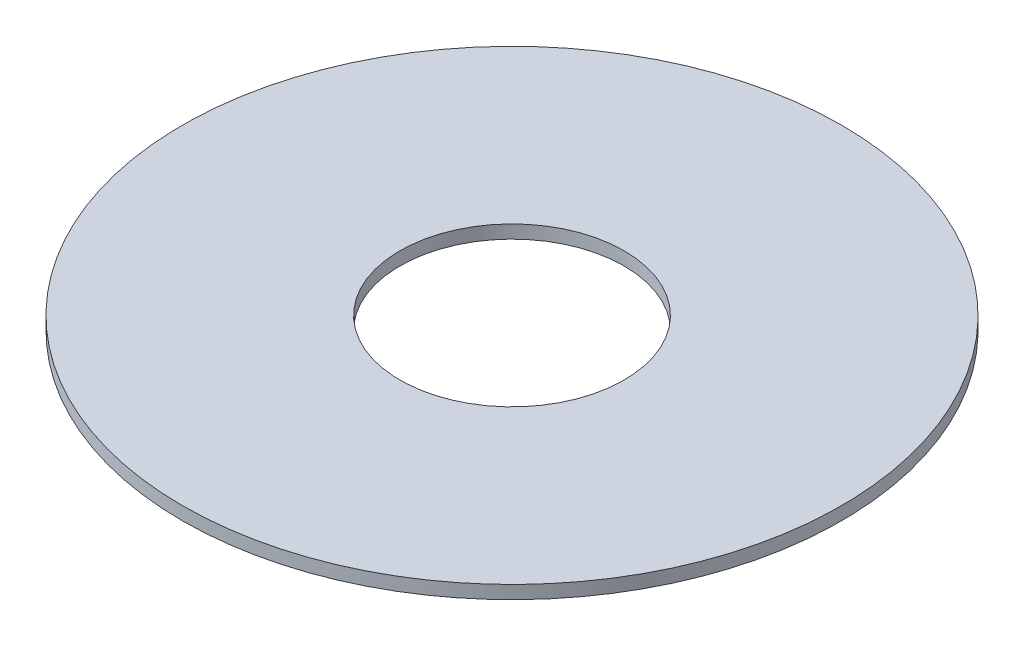
SolidWorks part; units mm, degrees
material "AISI 304"
ref_plane "Front Plane" through (0, 0, 0) normal (0, 0, 1) x (1, 0, 0)
ref_plane "Top Plane" through (0, 0, 0) normal (0, 1, 0) x (1, 0, 0)
ref_plane "Right Plane" through (0, 0, 0) normal (1, 0, 0) x (0, 0, -1)
other "Bounding Box"
ref_plane "Default Plane" through (0, 2.286, 19.05) normal (0, -1, 0) x (-1, 0, 0)
sketch "Sketch1" plane through (0, 0, 0) normal (0, 1, 0) x (1, 0, 0)
  circle A0 centre (0, 0) radius 19.05
  circle A1 centre (0, 0) radius 6.477
  dimension "D1" = 12.954
  dimension "D2" = 38.1
extrude "Boss-Extrude1" add sketch "Sketch1" along normal mid plane 0.762
equation "\"Unit Measure\"= \"BoundingVolume\" / \"Thickness\"'in^2"
